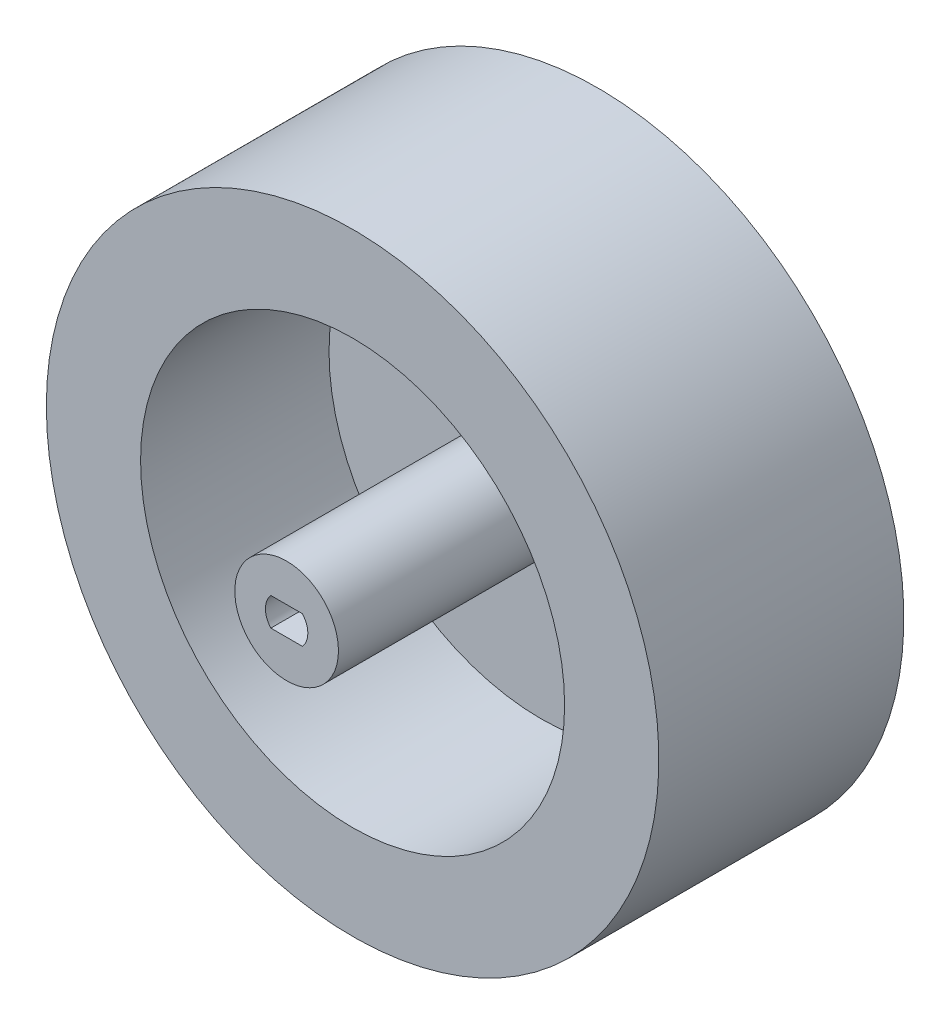
SolidWorks part; units mm, degrees
ref_plane "Front Plane" through (0, 0, 0) normal (0, 0, 1) x (1, 0, 0)
ref_plane "Top Plane" through (0, 0, 0) normal (0, 1, 0) x (1, 0, 0)
ref_plane "Right Plane" through (0, 0, 0) normal (1, 0, 0) x (0, 0, -1)
sketch "Sketch1" plane through (0, 0, 0) normal (0, 0, 1) x (1, 0, 0)
  circle A0 centre (0, 0) radius 32.5
  dimension "D1" = 65
extrude "Boss-Extrude1" add sketch "Sketch1" along normal blind 26
sketch "Sketch2" plane through (0, 0, 26) normal (0, 0, 1) x (1, 0, 0)
  circle A0 centre (0, 0) radius 22.5
  dimension "D1" = 45
extrude "Cut-Extrude1" cut sketch "Sketch2" against normal blind 20
sketch "Sketch3" plane through (0, 0, 6) normal (0, 0, 1) x (1, 0, 0)
  circle A0 centre (0, 0) radius 5.5
  dimension "D1" = 11
extrude "Boss-Extrude2" add sketch "Sketch3" along normal blind 27
sketch "Sketch4" plane through (0, 0, 33) normal (0, 0, 1) x (1, 0, 0)
  line L0 (-2.25, 0) -> (2.25, 0) construction
  line L1 (1.6771, 1.5) -> (-1.6771, 1.5)
  line L2 (1.6771, -1.5) -> (-1.6771, -1.5)
  circle A0 centre (0, 0) radius 2.25
  dimension "D1" = 4.5
  dimension "D2" = 1.5
extrude "Cut-Extrude2" cut sketch "Sketch4" against normal blind 24.3 contours L0 A0 L2 | A0 L0 L1 region at (0, 0.7165, 33) region at (0, -0.7165, 33)
